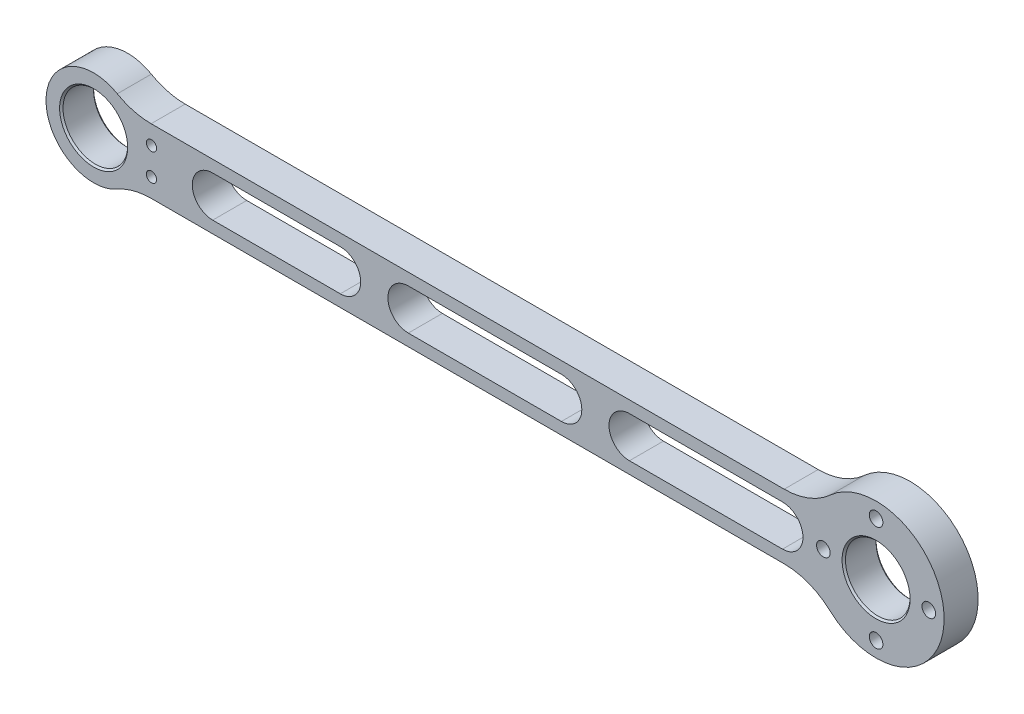
SolidWorks part; units mm, degrees
ref_plane "前视基准面" through (0, 0, 0) normal (0, 0, 1) x (1, 0, 0)
ref_plane "上视基准面" through (0, 0, 0) normal (0, 1, 0) x (1, 0, 0)
ref_plane "右视基准面" through (0, 0, 0) normal (1, 0, 0) x (0, 0, -1)
sketch "草图1" plane through (0, 0, 0) normal (0, 0, 1) x (1, 0, 0)
  line L0 (0, 0) -> (230, 0) construction
  line L1 (1.5589, 9.3712) -> (0, 9.5) construction
  line L2 (202.9861, -9.5) -> (20.8216, -9.5)
  line L4 (202.9861, 9.5) -> (21.6386, 9.5)
  line L6 (230, -9.5) -> (228.4411, -9.3712) construction
  line L7 (230, 9.5) -> (228.4411, 9.3712) construction
  line L8 (1.5589, -9.3712) -> (0, -9.5) construction
  line L9 (20.8216, -9.5) -> (16.9041, -9.5)
  line L10 (21.6386, 9.5) -> (16.9041, 9.5)
  circle A0 centre (0, 0) radius 9.5
  arc A1 (-0.2295, 13.9981) -> (3.4233, -13.575) centre (0, 0) ccw
  circle A2 centre (230, 0) radius 9.5
  arc A3 (214.8013, -13) -> (214.8013, 13) centre (230, 0) ccw
  arc A7 (6.9605, 12.1471) -> (6.9605, -12.1471) centre (0, 0) ccw
  arc A8 (6.9605, -12.1471) -> (16.9041, -9.5) centre (16.9041, -29.5) cw
  arc A9 (6.9605, 12.1471) -> (16.9041, 9.5) centre (16.9041, 29.5) ccw
  arc A10 (216.4931, -14.75) -> (216.4931, 14.75) centre (230, 0) ccw
  arc A11 (202.9861, -9.5) -> (216.4931, -14.75) centre (202.9861, -29.5) cw
  arc A12 (216.4931, 14.75) -> (202.9861, 9.5) centre (202.9861, 29.5) cw
  point P7 (115, 0)
  dimension "D1" = 19
  dimension "D2" = 28
  dimension "D3" = 20
  dimension "D4" = 19
  dimension "D5" = 20
  dimension "D8" = 20
  dimension "D6" = 9.5
  dimension "D7" = 9.5
extrude "凸台-拉伸2" add sketch "草图1" along normal blind 10 contours A1 L2 A3 L4 A2 A0 region at (127.347, 0, 0)
chamfer "倒角1" distance 0.5 angle 45 2 edges at (9.5, 0, 10) (9.5, 0, 0)
sketch "草图2" plane through (0, 0, 10) normal (0, 0, 1) x (1, 0, 0)
  line L0 (0, 0) -> (21.5, 0) construction
  line L1 (115, -1.5) -> (115, 9.5) construction
  line L2 (202.9861, 9.5) -> (16.9041, 9.5) construction
  line L3 (115, -1.5) -> (137.5, -6) construction
  line L4 (92.5, -6) -> (137.5, -6)
  line L6 (92.5, 6) -> (137.5, 6)
  line L8 (115, -1.5) -> (135.7692, 2.6538) construction
  line L9 (21.5, 0) -> (50, 0) construction
  line L10 (157.5, -6) -> (202.5, -6)
  line L12 (157.5, 6) -> (202.5, 6)
  line L16 (35, -6) -> (72.5, -6)
  line L18 (35, 6) -> (72.5, 6)
  line L21 (50, 0) -> (157.5, 0) construction
  line L22 (162, 0) -> (230, 0) construction
  arc A2 (92.5, 6) -> (92.5, -6) centre (92.5, 0) ccw
  arc A3 (137.5, -6) -> (137.5, 6) centre (137.5, 0) ccw
  arc A4 (157.5, 6) -> (157.5, -6) centre (157.5, 0) ccw
  arc A6 (72.5, -6) -> (72.5, 6) centre (72.5, 0) ccw
  arc A7 (202.5, -6) -> (202.5, 6) centre (202.5, 0) ccw
  arc A8 (35, 6) -> (35, -6) centre (35, 0) ccw
  point P12 (180, 0)
  point P17 (50, 0)
  dimension "D7" = 15
  dimension "D1" = 12
  dimension "D2" = 12
  dimension "D3" = 45
  dimension "D5" = 45
  dimension "D6" = 12
extrude "切除-拉伸1" cut sketch "草图2" against normal blind 10
sketch "草图3" plane through (0, 0, 10) normal (0, 0, 1) x (1, 0, 0)
  line L0 (230, 0) -> (243, 0) construction
  line L1 (230, 0) -> (236.5, 11.2583) construction
  line L2 (230, 0) -> (223.5, 11.2583) construction
  arc A8 (220.8385, 11.8771) -> (215.1333, 1.9956) centre (230, 0) ccw
  circle A9 centre (215, 0) radius 2
  circle A12 centre (245, 0) radius 2
  circle A13 centre (237.5, 12.9904) radius 2
  circle A14 centre (222.5, 12.9904) radius 2
  arc A15 (235.7051, 13.8727) -> (224.2949, 13.8727) centre (230, 0) ccw
  arc A16 (244.8667, 1.9956) -> (239.1615, 11.8771) centre (230, 0) ccw
  arc A17 (215.1333, -1.9956) -> (220.8385, -11.8771) centre (230, 0) ccw
  circle A18 centre (237.5, -12.9904) radius 2
  circle A19 centre (222.5, -12.9904) radius 2
  arc A20 (224.2949, -13.8727) -> (235.7051, -13.8727) centre (230, 0) ccw
  arc A21 (239.1615, -11.8771) -> (244.8667, -1.9956) centre (230, 0) ccw
  point P18 (230, 0)
  dimension "D1" = 60
  dimension "D2" = 60
extrude "切除-拉伸2" cut sketch "草图3" against normal blind 10 contours A12 | A14 | A13 region at (222.5, 12.9904, 10) region at (237.5, 12.9904, 10) region at (245, 0, 10)
chamfer "倒角2" distance 0.5 angle 45 1 edges at (239.5, 0, 10)
sketch "草图5" plane through (0, 0, 10) normal (0, 0, 1) x (1, 0, 0)
  line L0 (230, 0) -> (222.5, 12.9904) construction
  line L1 (230, 0) -> (221.3397, -5) construction
  arc A0 (215.1333, -1.9956) -> (220.8385, -11.8771) centre (230, 0) ccw
  circle A1 centre (245, 0) radius 2 construction
  circle A2 centre (237.5, 12.9904) radius 2 construction
  circle A3 centre (222.5, 12.9904) radius 2 construction
  circle A4 centre (245, 0) radius 2
  circle A5 centre (237.5, 12.9904) radius 2
  circle A6 centre (222.5, 12.9904) radius 2
  circle A7 centre (222.5, -12.9904) radius 2
  circle A8 centre (215, 0) radius 2
  circle A9 centre (230, 0) radius 10 construction
  circle A10 centre (237.5, -12.9904) radius 2
  arc A11 (224.2949, -13.8727) -> (235.7051, -13.8727) centre (230, 0) ccw
  arc A12 (239.1615, -11.8771) -> (215.1333, 1.9956) centre (230, 0) ccw
extrude "切除-拉伸3" cut sketch "草图5" against normal blind 10 contours A8 | A7 | A10 region at (215, 0, 10) region at (222.5, -12.9904, 10) region at (237.5, -12.9904, 10)
chamfer "倒角3" distance 0.5 angle 45 1 edges at (239.5, 0, 0)
ref_axis "基准轴1" through (230, 0, 9.5) along (0, 0, -1)
ref_axis "基准轴2" through (230, 0, 9.5) along (0, 0, -1)
ref_plane "基准面1" through (6.9353, 39.3323, 0) normal (0.1736, 0.9848, 0) x (0, 0, -1)
sketch "草图9" plane through (0, 0, 10) normal (0, 0, 1) x (1, 0, 0)
  circle A0 centre (215, 0) radius 2
  circle A1 centre (222.5, 12.9904) radius 2
  circle A2 centre (237.5, 12.9904) radius 2
  circle A3 centre (245, 0) radius 2
  circle A4 centre (237.5, -12.9904) radius 2
  circle A5 centre (222.5, -12.9904) radius 2
extrude "凸台-拉伸3" add sketch "草图9" against normal blind 10
sketch "草图10" plane through (0, 0, 10) normal (0, 0, 1) x (1, 0, 0)
  arc A0 (228.0042, 15.371) -> (214.629, 1.9958) centre (230, 0) ccw
  circle A1 centre (214.5, 0) radius 2
  arc A2 (214.629, -1.9958) -> (231.9958, 15.371) centre (230, 0) ccw
ref_axis "基准轴3" through (230, 0, 9.5) along (0, 0, -1)
extrude "切除-拉伸6" cut sketch "草图10" against normal blind 10 contours A1 region at (214.5, 0, 10)
pattern_circular "阵列(圆周)2" count 4 over 360 about axis through (230, 0, 9.5) along (0, 0, -1) of "切除-拉伸6"
sketch "草图11" plane through (0, 0, 10) normal (0, 0, 1) x (1, 0, 0)
  line L0 (0, 0) -> (17, 0) construction
  line L1 (17, 0) -> (17, 4) construction
  line L2 (17, 0) -> (17, -4) construction
  circle A0 centre (17, 4) radius 1.5
  circle A1 centre (17, -4) radius 1.5
extrude "切除-拉伸7" cut sketch "草图11" against normal through all
